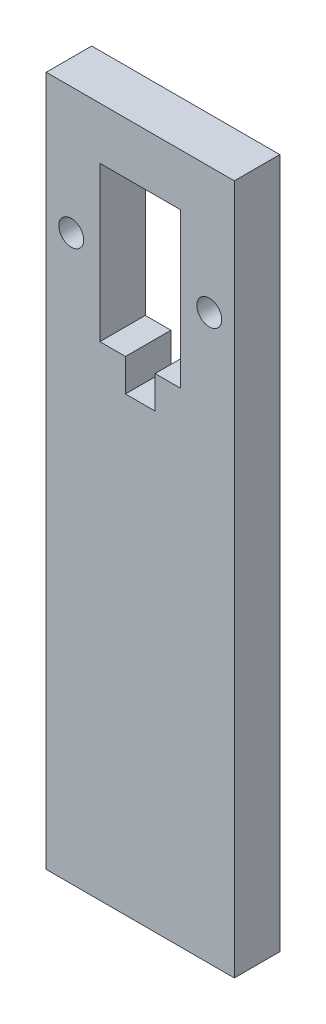
SolidWorks part; units mm, degrees
ref_plane "Front Plane" through (0, 0, 0) normal (0, 0, 1) x (1, 0, 0)
ref_plane "Top Plane" through (0, 0, 0) normal (0, 1, 0) x (1, 0, 0)
ref_plane "Right Plane" through (0, 0, 0) normal (1, 0, 0) x (0, 0, -1)
sketch "Sketch1" plane through (0, 0, 0) normal (0, 0, 1) x (1, 0, 0)
  line L1 (-18.5582, 31.0897) -> (10.4018, 31.0897)
  line L2 (-18.5582, 31.0897) -> (-18.5582, -43.4103)
  line L3 (-18.5582, -43.4103) -> (10.4018, -43.4103)
  line L4 (10.4018, 31.0897) -> (10.4018, -43.4103)
  dimension "D1" = 28.96
  dimension "D2" = 74.5
extrude "Boss-Extrude1" add sketch "Sketch1" along normal blind 7
sketch "Sketch2" plane through (0, 31.0897, 0) normal (0, 1, 0) x (1, 0, 0)
  line L0 (-18.5582, 0) -> (-10.3032, 0)
  line L1 (10.4018, 0) -> (-18.5582, 0) construction
  line L2 (-10.3032, 0) -> (-10.3032, -7)
  line L3 (10.4018, -7) -> (-18.5582, -7) construction
  line L4 (-10.3032, -7) -> (-18.5582, -7)
  line L5 (-18.5582, -7) -> (-18.5582, 0)
  line L6 (10.4018, 0) -> (2.1468, 0)
  line L7 (2.1468, 0) -> (2.1468, -7)
  line L8 (2.1468, -7) -> (10.4018, -7)
  line L9 (10.4018, -7) -> (10.4018, 0)
  dimension "D1" = 12.45
extrude "Boss-Extrude2" add sketch "Sketch2" along normal blind 23.8
sketch "Sketch3" plane through (0, 54.8897, 0) normal (0, 1, 0) x (1, 0, 0)
  line L1 (-18.5582, 0) -> (10.4018, 0)
  line L2 (-18.5582, 0) -> (-18.5582, -7)
  line L3 (-18.5582, -7) -> (10.4018, -7)
  line L4 (10.4018, 0) -> (10.4018, -7)
extrude "Boss-Extrude3" add sketch "Sketch3" along normal blind 8
sketch "Sketch4" plane through (0, 31.0897, 0) normal (0, 1, 0) x (1, 0, 0)
  line L0 (10.4018, 0) -> (-18.5582, 0) construction
  line L1 (-6.3582, 0) -> (-1.7982, 0)
  line L2 (-6.3582, 0) -> (-6.3582, -7)
  line L3 (-6.3582, -7) -> (-1.7982, -7)
  line L4 (-1.7982, 0) -> (-1.7982, -7)
  line L5 (-18.5582, -7) -> (10.4018, -7) construction
  line L6 (-18.5582, 0) -> (-18.5582, -7) construction
  line L7 (10.4018, -7) -> (10.4018, 0) construction
  dimension "D1" = 12.2
  dimension "D2" = 12.2
extrude "Cut-Extrude1" cut sketch "Sketch4" against normal blind 5
sketch "Sketch5" plane through (0, 0, 7) normal (0, 0, 1) x (1, 0, 0)
  line L0 (-18.5582, 62.8897) -> (10.4018, 62.8897) construction
  line L1 (2.1468, 54.8897) -> (2.1468, 31.0897) construction
  line L2 (-10.3032, 54.8897) -> (-10.3032, 31.0897) construction
  circle A0 centre (-14.7032, 43.4097) radius 1.92
  circle A1 centre (6.5468, 43.4097) radius 1.92
  dimension "D1" = 3.84
  dimension "D2" = 19.48
  dimension "D3" = 19.48
  dimension "D4" = 4.4
  dimension "D5" = 4.4
extrude "Cut-Extrude2" cut sketch "Sketch5" against normal blind 10
